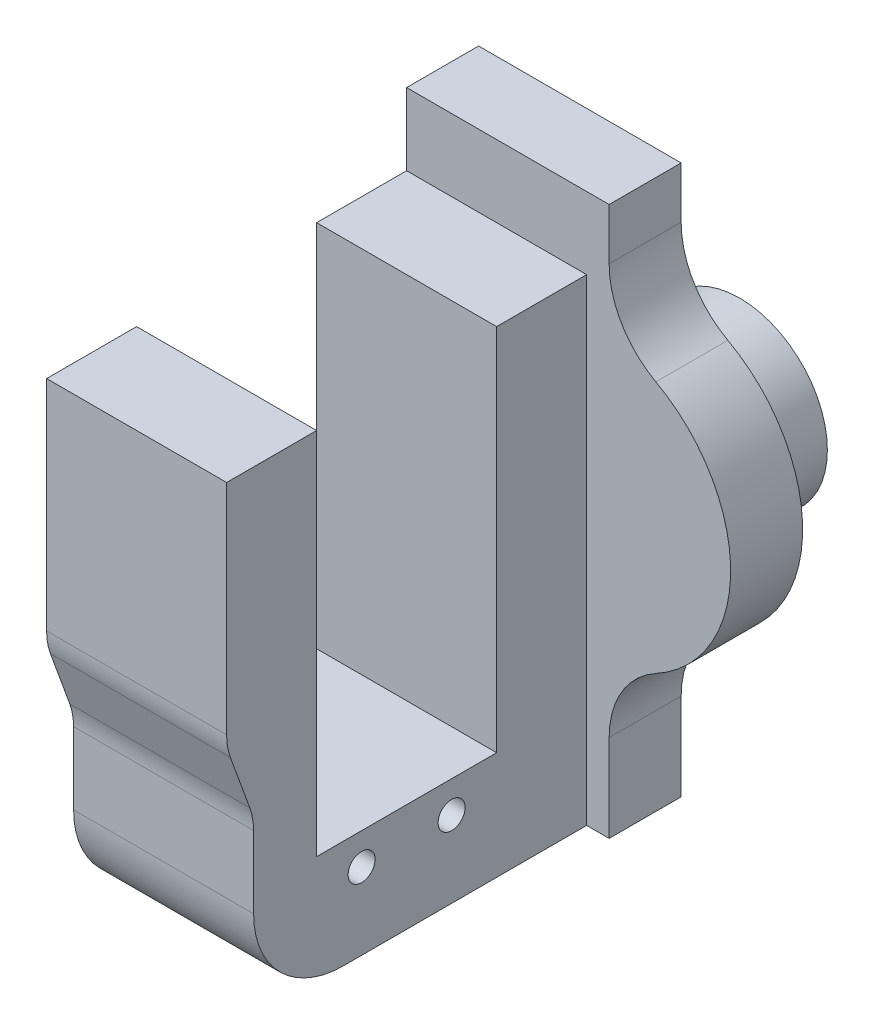
SolidWorks part; units mm, degrees
ref_plane "Front Plane" through (0, 0, 0) normal (0, 0, 1) x (1, 0, 0)
ref_plane "Top Plane" through (0, 0, 0) normal (0, 1, 0) x (1, 0, 0)
ref_plane "Right Plane" through (0, 0, 0) normal (1, 0, 0) x (0, 0, -1)
sketch "Sketch3" plane through (0, 0, 30) normal (0, 0, -1) x (-1, 0, 0)
  line L0 (95, 33.2573) -> (65, 33.2573) construction
  line L15 (80, 53.2573) -> (80, 33.2573) construction
  line L20 (55, 53.2573) -> (105, 53.2573)
  line L29 (55, -26.7427) -> (105, -26.7427)
  line L31 (110, -21.7427) -> (110, 48.2573)
  line L33 (50, -21.7427) -> (50, 48.2573)
  arc A17 (50, 48.2573) -> (55, 53.2573) centre (55, 48.2573) cw
  arc A18 (110, 48.2573) -> (105, 53.2573) centre (105, 48.2573) ccw
  arc A21 (50, -21.7427) -> (55, -26.7427) centre (55, -21.7427) ccw
  arc A22 (110, -21.7427) -> (105, -26.7427) centre (105, -21.7427) cw
  dimension "D1" = 5
extrude "Boss-Extrude1" add sketch "Sketch3" along normal blind 8
ref_plane "Plane1" through (-80, 0, 0) normal (-1, 0, 0) x (0, 0, 1)
sketch "Sketch8" plane through (0, 0, 22) normal (0, 0, -1) x (-1, 0, 0)
  line L0 (50, 13.2573) -> (110, 13.2573) construction
  line L1 (50, 48.2573) -> (50, -21.7427) construction
  line L2 (110, -21.7427) -> (110, 48.2573) construction
  line L3 (80, 13.2573) -> (80, -26.7427) construction
  line L4 (55, -26.7427) -> (105, -26.7427) construction
  line L5 (78.25, 15.3786) -> (78.25, 11.136)
  line L6 (81.75, 15.3786) -> (81.75, 11.136)
  arc A0 (78.25, 11.136) -> (81.75, 11.136) centre (80, 13.2573) ccw
  arc A1 (81.75, 15.3786) -> (78.25, 15.3786) centre (80, 13.2573) ccw
extrude "Cut-Extrude3" cut sketch "Sketch8" against normal blind 3
sketch "Sketch10" plane through (0, 0, 22) normal (0, 0, -1) x (-1, 0, 0)
  line L0 (50, 13.2573) -> (110, 13.2573) construction
  line L1 (50, 48.2573) -> (50, -21.7427) construction
  line L2 (110, -21.7427) -> (110, 48.2573) construction
  line L3 (80, 13.2573) -> (80, -26.7427) construction
  line L4 (55, -26.7427) -> (105, -26.7427) construction
  line L7 (81.75, 11.136) -> (81.75, 15.3786)
  line L8 (78.25, 15.3786) -> (78.25, 11.136)
  line L9 (81.75, 11.136) -> (81.75, 15.3786)
  line L10 (78.25, 15.3786) -> (78.25, 11.136)
  circle A3 centre (80, 13.2573) radius 9.75
  arc A5 (78.25, 11.136) -> (81.75, 11.136) centre (80, 13.2573) ccw
  arc A6 (81.75, 15.3786) -> (78.25, 15.3786) centre (80, 13.2573) ccw
  arc A7 (78.25, 11.136) -> (81.75, 11.136) centre (80, 13.2573) ccw
  arc A8 (81.75, 15.3786) -> (78.25, 15.3786) centre (80, 13.2573) ccw
  dimension "D1" = 0
extrude "Boss-Extrude4" add sketch "Sketch10" along normal blind 9
sketch "Sketch12" plane through (-80, 0, 0) normal (-1, 0, 0) x (0, 0, 1)
  line L0 (30, -19.2427) -> (30, 33.7573)
  line L2 (30, -21.7427) -> (30, 48.2573) construction
  line L21 (40, 33.7573) -> (40, -7.2427)
  line L22 (40, -7.2427) -> (60, -7.2427)
  line L24 (67.0011, -19.2427) -> (30, -19.2427)
  line L25 (40, -6.9927) -> (40, 33.5073) construction
  line L27 (60, -6.9927) -> (40, -6.9927) construction
  line L35 (60, 39.4573) -> (60, 33.5073) construction
  line L36 (60, 33.7573) -> (60, -7.2427)
  line L40 (60, 33.7573) -> (70, 33.7573)
  line L41 (40, 33.7573) -> (30, 33.7573)
  line L42 (70, 33.7573) -> (70, 8.2394)
  line L43 (70, 8.2394) -> (67.0011, 0)
  line L44 (67.0011, 0) -> (67.0011, -19.2427)
  dimension "D1" = 0
  dimension "D2" = 10
  dimension "D3" = 0.25
  dimension "D4" = 160
extrude "Boss-Extrude5" add sketch "Sketch12" along normal blind 20
sketch "Sketch13" plane through (-80, 0, 0) normal (1, 0, 0) x (0, 0, -1)
  circle A0 centre (-55, -10.7427) radius 1.5
  circle A1 centre (-45, -10.7427) radius 1.5
  circle A2 centre (-55, 37.2573) radius 1.5
  circle A3 centre (-45, 37.2573) radius 1.5
extrude "Cut-Extrude4" cut sketch "Sketch13" against normal blind 10
sketch "Sketch14" plane through (0, 0, 22) normal (0, 0, -1) x (-1, 0, 0)
  circle A0 centre (80, 13.2573) radius 12
extrude "Boss-Extrude6" add sketch "Sketch14" along normal blind 1
fillet "Fillet4" radius 10 1 edges at (-90, -19.2427, 67.0011)
fillet "Fillet5" radius 7 2 edges at (-90, 8.2394, 70) (-90, 0, 67.0011)
sketch "Sketch15" plane through (0, 0, 30) normal (0, 0, 1) x (1, 0, 0)
  line L0 (-77.5, 41.7573) -> (-77.5, 29.0608)
  line L1 (-100, -19.2427) -> (-77.5, -19.2427)
  line L2 (-100, -19.2427) -> (-100, 41.7573)
  line L3 (-100, 41.7573) -> (-77.5, 41.7573)
  line L5 (-78, 39.4573) -> (-78, 41.4573) construction
  line L6 (-77.5, -2.5462) -> (-77.5, -19.2427)
  arc A1 (-77.5, -2.5462) -> (-77.5, 29.0608) centre (-80, 13.2573) ccw
  dimension "D1" = 0.5
extrude "Cut-Extrude5" cut sketch "Sketch15" against normal through all flip side to cut
fillet "Fillet6" radius 10 2 edges at (-77.5, -2.5462, 26) (-77.5, 29.0608, 26)
